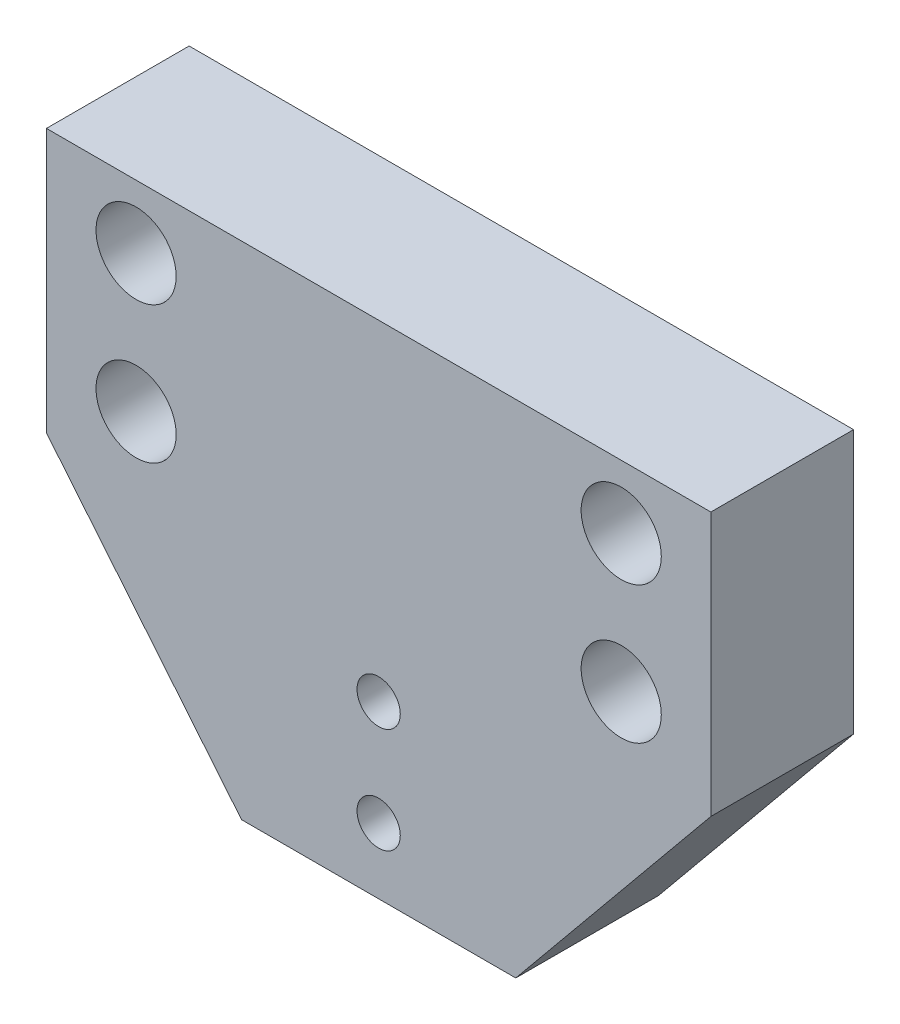
SolidWorks part; units mm, degrees
ref_plane "Front Plane" through (0, 0, 0) normal (0, 0, 1) x (1, 0, 0)
ref_plane "Top Plane" through (0, 0, 0) normal (0, 1, 0) x (1, 0, 0)
ref_plane "Right Plane" through (0, 0, 0) normal (1, 0, 0) x (0, 0, -1)
sketch "Sketch1" plane through (0, 0, 0) normal (0, 0, 1) x (1, 0, 0)
  line L0 (0, 0) -> (0, 60.5723) construction
  line L1 (0, -55) -> (0, 55) construction
  line L2 (0, 0) -> (-55.7657, 0) construction
  line L3 (31.5, 10) -> (-31.5, 10)
  line L4 (-31.5, 10) -> (-31.5, -15)
  line L5 (-31.5, -15) -> (31.5, -15)
  line L6 (31.5, 10) -> (31.5, -15)
  line L7 (0, -37.5157) -> (-13, -37.5157)
  line L8 (0, -37.5157) -> (13, -37.5157)
  line L9 (-13, -37.5157) -> (-31.5, -15)
  line L10 (13, -37.5157) -> (31.5, -15)
  line L11 (55, 0) -> (-55, 0) construction
  circle A4 centre (0, -21.3221) radius 2.05
  circle A5 centre (0, -31.3) radius 2.05
  circle A6 centre (-23, 4) radius 3.3
  circle A7 centre (-23, 4) radius 3.8
  circle A8 centre (-23, -9) radius 3.3
  circle A9 centre (-23, -9) radius 3.8
  circle A10 centre (23, -9) radius 3.8
  circle A11 centre (23, -9) radius 3.3
  circle A12 centre (23, 4) radius 3.3
  circle A13 centre (23, 4) radius 3.8
  point P5 (-23, 4)
  point P6 (-23, -9)
  point P12 (0, -37.5157)
  point P17 (0, -15)
  point P21 (0, 10)
  dimension "D3" = 13
  dimension "D7" = 6
  dimension "D8" = 6.6
  dimension "D9" = 4.1
  dimension "D10" = 4.1
  dimension "D11" = 46
  dimension "D2" = 6
  dimension "D4" = 63
  dimension "D5" = 25
  dimension "D6" = 13
extrude "Boss-Extrude1" add sketch "Sketch1" along normal blind 13.53 contours L6 L3 L4 L5 A8 region at (0, -2.5, 0)
extrude "Boss-Extrude2" add sketch "Sketch1<3>" along normal blind 13.53 contours L8 L10 L5 L9 L7 A5 A4 region at (0, -24.6541, 0)
sketch "Sketch1<3>" plane through (0, 0, 0) normal (0, 0, 1) x (1, 0, 0) same geometry as "Sketch1"
